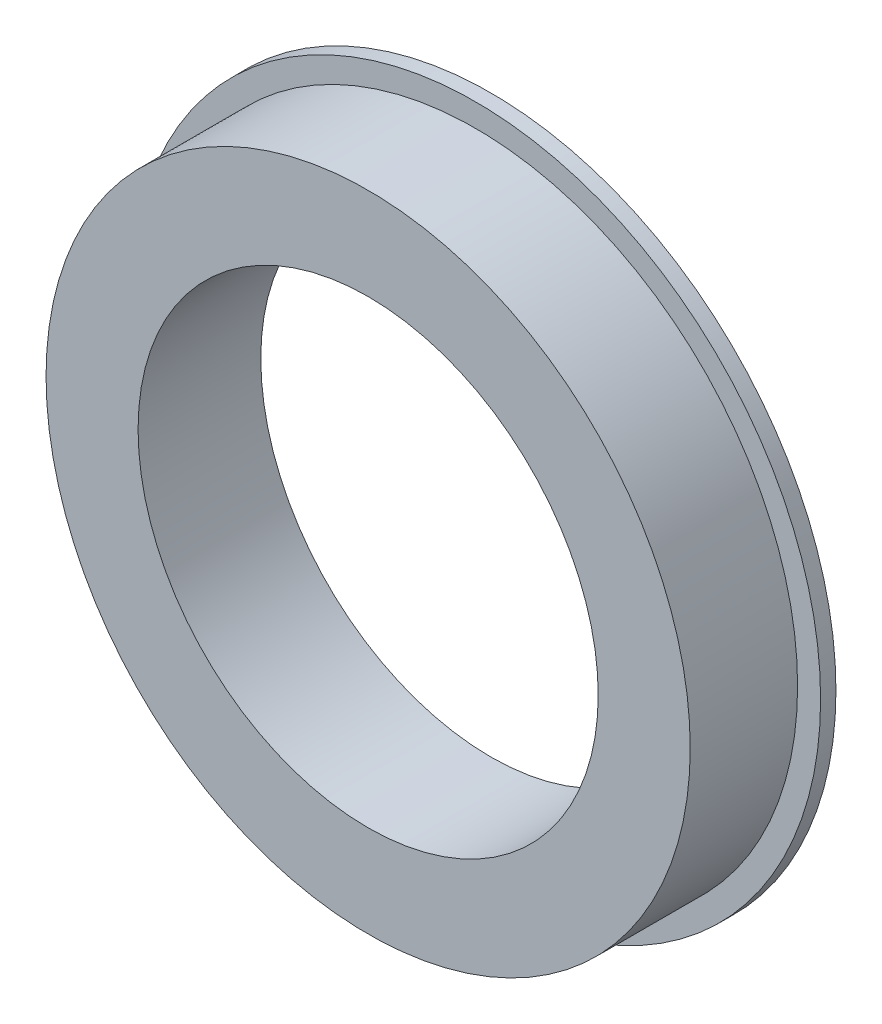
SolidWorks part; units mm, degrees
ref_plane "Front Plane" through (0, 0, 0) normal (0, 0, 1) x (1, 0, 0)
ref_plane "Top Plane" through (0, 0, 0) normal (0, 1, 0) x (1, 0, 0)
ref_plane "Right Plane" through (0, 0, 0) normal (1, 0, 0) x (0, 0, -1)
sketch "Sketch1" plane through (0, 0, 0) normal (0, 0, 1) x (1, 0, 0)
  circle A0 centre (0, 0) radius 10.5
  circle A1 centre (0, 0) radius 11.25
  circle A2 centre (0, 0) radius 7.5
  dimension "D1" = 21
  dimension "D2" = 22.5
  dimension "D3" = 15
extrude "Boss-Extrude1" add sketch "Sketch1" along normal blind 4 contours A0 A2 region at (-10.203, 0, 0)
extrude "Boss-Extrude2" add sketch "Sketch1<3>" along normal blind 0.5 contours A1 A0 region at (-10.9318, 0, 0)
sketch "Sketch1<3>" plane through (0, 0, 0) normal (0, 0, 1) x (1, 0, 0) same geometry as "Sketch1"
